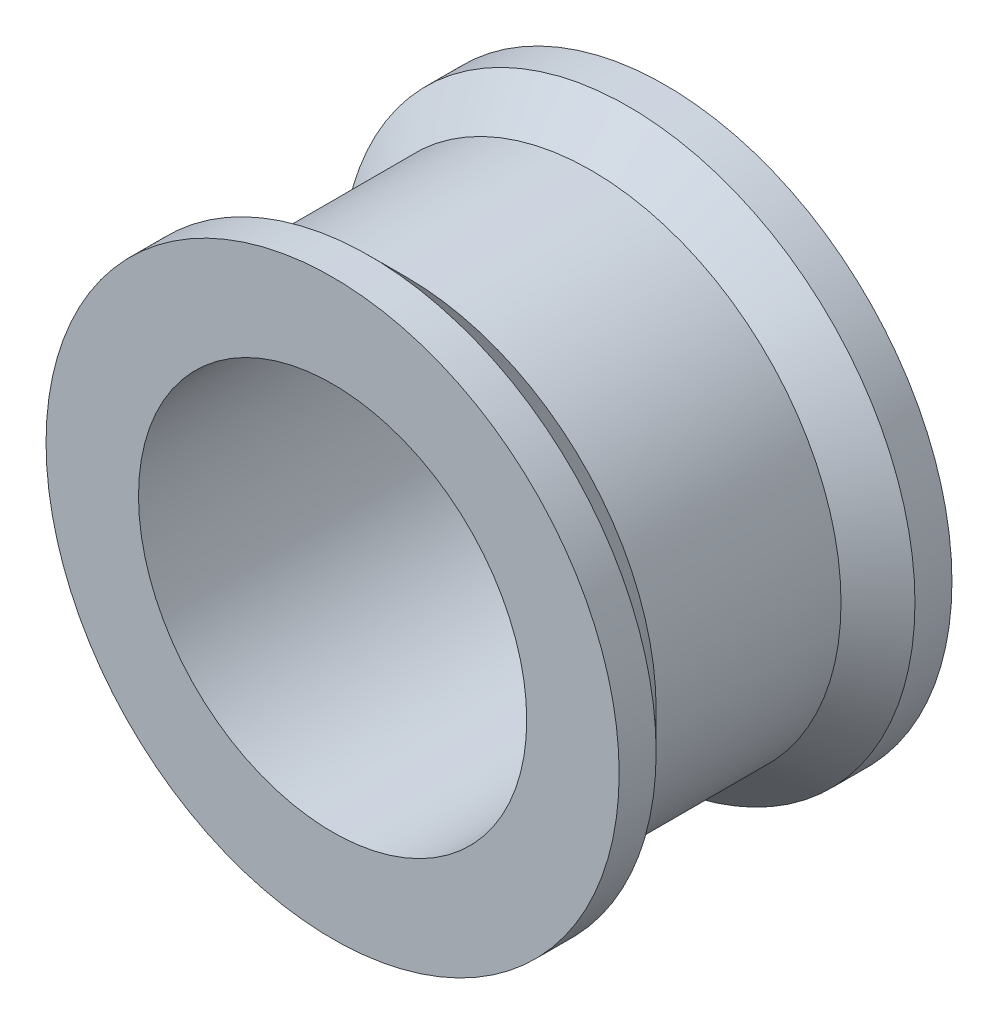
SolidWorks part; units mm, degrees
ref_plane "Front Plane" through (0, 0, 0) normal (0, 0, 1) x (1, 0, 0)
ref_plane "Top Plane" through (0, 0, 0) normal (0, 1, 0) x (1, 0, 0)
ref_plane "Right Plane" through (0, 0, 0) normal (1, 0, 0) x (0, 0, -1)
sketch "Sketch1" plane through (0, 0, 0) normal (0, 0, 1) x (1, 0, 0)
  circle A0 centre (0, 0) radius 5.25
  circle A1 centre (0, 0) radius 7.75
  dimension "D1" = 10.5
  dimension "D2" = 15.5
extrude "Boss-Extrude1" add sketch "Sketch1" along normal blind 1
sketch "Sketch2" plane through (0, 0, 1) normal (0, 0, 1) x (1, 0, 0)
  circle A0 centre (0, 0) radius 5.25
  circle A1 centre (0, 0) radius 6.75
  circle A2 centre (0, 0) radius 5.25 construction
  dimension "D1" = 13.5
extrude "Boss-Extrude2" add sketch "Sketch2" along normal blind 3.5
chamfer "Chamfer1" distance 1 angle 45 1 edges at (6.75, 0, 1)
mirror "Mirror5" about plane through (0, 0, 4.5) normal (0, 0, 1) of bodies 102
